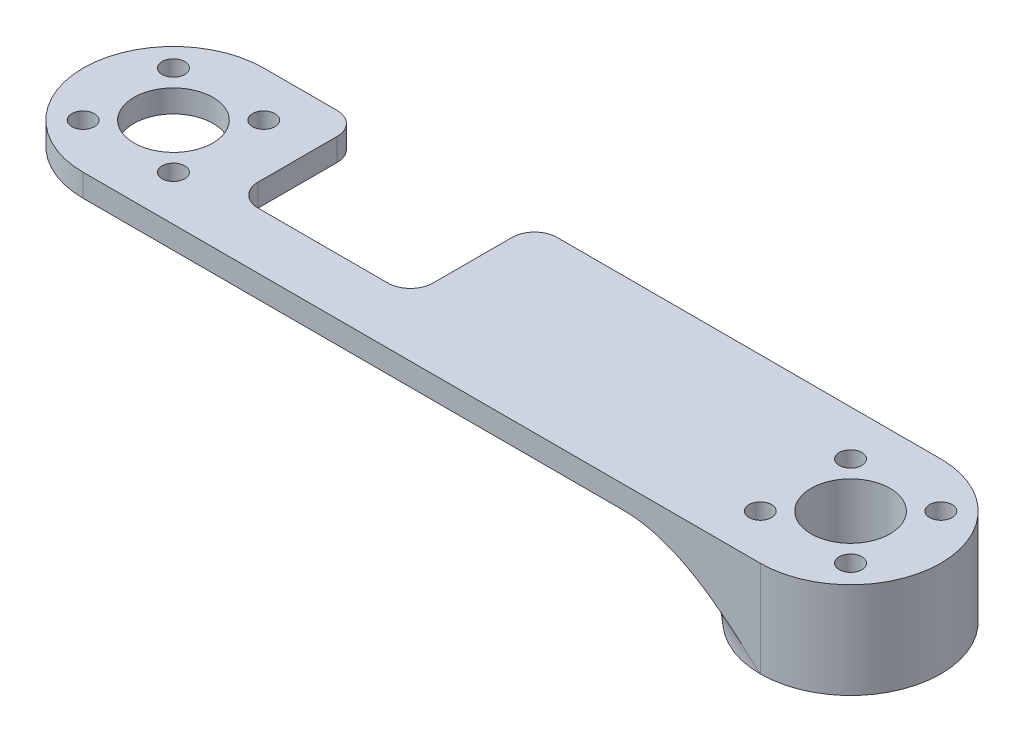
SolidWorks part; units mm, degrees
ref_plane "Front Plane" through (0, 0, 0) normal (0, 0, 1) x (1, 0, 0)
ref_plane "Top Plane" through (0, 0, 0) normal (0, 1, 0) x (1, 0, 0)
ref_plane "Right Plane" through (0, 0, 0) normal (1, 0, 0) x (0, 0, -1)
sketch "Sketch1" plane through (0, 0, 0) normal (0, 1, 0) x (1, 0, 0)
  line L0 (-60, 0) -> (60, 0) construction
  line L1 (-60, 16) -> (-43, 16)
  line L2 (-60, -16) -> (-43, -16)
  line L3 (-43, 6) -> (-43, -6)
  line L4 (-68, -8) -> (-52, -8) construction
  line L5 (-68, -8) -> (-68, 8) construction
  line L6 (-68, 8) -> (-52, 8) construction
  line L7 (-52, -8) -> (-52, 8) construction
  line L8 (-60, 8) -> (-60, -8) construction
  line L9 (-68, 0) -> (-52, 0) construction
  line L10 (52, -8) -> (68, -8) construction
  line L11 (52, -8) -> (52, 8) construction
  line L12 (52, 8) -> (68, 8) construction
  line L13 (68, -8) -> (68, 8) construction
  line L14 (60, 8) -> (60, -8) construction
  line L15 (52, 0) -> (68, 0) construction
  line L17 (-12, 6) -> (-12, -6)
  line L18 (4, -16) -> (60, -16)
  line L19 (-43, -16) -> (4, -16)
  line L20 (-43, -6) -> (-12, -6)
  line L21 (-43, 16) -> (-43, 6)
  line L22 (-12, 16) -> (-12, 6)
  line L23 (-12, 16) -> (60, 16)
  arc A0 (-60, 16) -> (-60, -16) centre (-60, 0) ccw
  arc A1 (60, -16) -> (60, 16) centre (60, 0) ccw
  circle A2 centre (-52, 8) radius 2
  circle A3 centre (-52, -8) radius 2
  circle A4 centre (-68, -8) radius 2
  circle A5 centre (-68, 8) radius 2
  circle A6 centre (52, 8) radius 2
  circle A7 centre (68, 8) radius 2
  circle A8 centre (68, -8) radius 2
  circle A9 centre (52, -8) radius 2
  circle A10 centre (-60, 0) radius 7
  circle A11 centre (60, 0) radius 7
  point P2 (0, 0)
  point P8 (-60, 0)
  point P12 (60, 0)
  dimension "D2" = 16
  dimension "D3" = 4
  dimension "D6" = 14
  dimension "D7" = 14
  dimension "D1" = 120
  dimension "D4" = 16
  dimension "D5" = 16
  dimension "D9" = 17
  dimension "D10" = 48
  dimension "D11" = 10
extrude "Boss-Extrude1" add sketch "Sketch1" along normal blind 4
fillet "Fillet1" radius 4 4 edges at (-43, 2, 6) (-12, 2, 6) (-12, 2, -16) (-43, 2, -16)
sketch "Sketch2" plane through (0, 0, 0) normal (0, 1, 0) x (1, 0, 0)
  circle A0 centre (60, 0) radius 16
  circle A1 centre (60, 0) radius 7
  circle A2 centre (52, 8) radius 2
  circle A3 centre (68, 8) radius 2
  circle A4 centre (52, -8) radius 2
  circle A5 centre (52, -8) radius 2 construction
  circle A6 centre (68, -8) radius 2
  point P18 (52, 8)
extrude "Boss-Extrude2" add sketch "Sketch2" against normal blind 13
fillet "Fillet2" radius 13 1 edges at (44, 0, 0)
